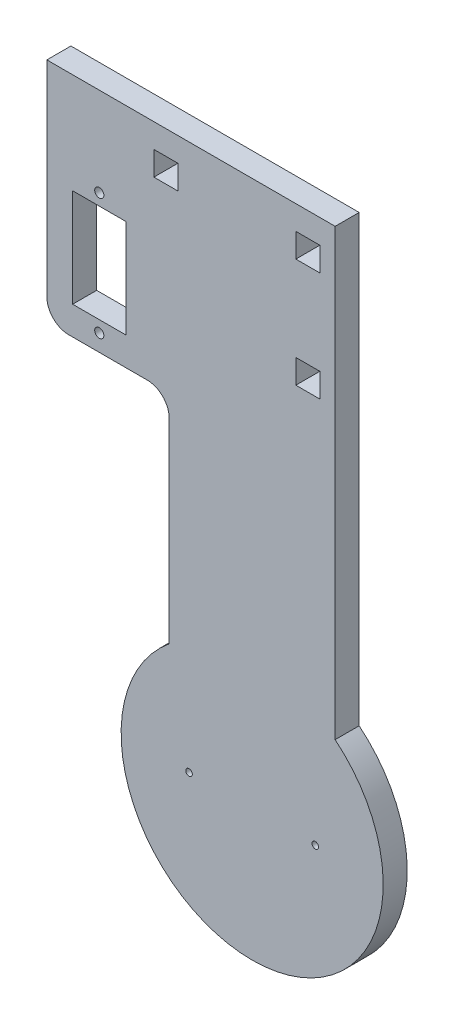
SolidWorks part; units mm, degrees
material "ﾁｰｸ材"
ref_plane "正面" through (0, 0, 0) normal (0, 0, 1) x (1, 0, 0)
ref_plane "平面" through (0, 0, 0) normal (0, 1, 0) x (1, 0, 0)
ref_plane "右側面" through (0, 0, 0) normal (1, 0, 0) x (0, 0, -1)
sketch "ｽｹｯﾁ1" plane through (0, 0, 0) normal (0, 0, 1) x (1, 0, 0)
  line L0 (19, 125) -> (-47, 125)
  line L1 (-19, 73) -> (-19, 23.2164)
  line L2 (19, 125) -> (19, 23.2164)
  line L4 (-47, 125) -> (-47, 73)
  line L6 (-47, 73) -> (-19, 73)
  arc A0 (-19, 23.2164) -> (19, 23.2164) centre (0, 0) ccw
  point P8 (-19, 75.5757)
  dimension "D1" = 60
  dimension "D2" = 125
  dimension "D3" = 19
  dimension "D4" = 47
  dimension "D5" = 52
extrude "ﾎﾞｽ - 押し出し1" add sketch "ｽｹｯﾁ1" along normal blind 5.5
sketch "ｽｹｯﾁ2" plane through (0, 0, 5.5) normal (0, 0, 1) x (1, 0, 0)
  line L0 (19, 125) -> (-47, 125) construction
  line L1 (-28.9, 79.5) -> (-41.1, 79.5)
  line L2 (-28.9, 79.5) -> (-28.9, 102)
  line L3 (-28.9, 102) -> (-41.1, 102)
  line L4 (-41.1, 79.5) -> (-41.1, 102)
  line L5 (-28.9, 79.5) -> (-41.1, 102) construction
  line L6 (-28.9, 102) -> (-41.1, 79.5) construction
  point P0 (-35, 90.75)
  dimension "D1" = 12.2
  dimension "D2" = 22.5
  dimension "D3" = 35
  dimension "D4" = 23
extrude "ｶｯﾄ - 押し出し1" cut sketch "ｽｹｯﾁ2" against normal through all
sketch "ｽｹｯﾁ3" plane through (0, 0, 5.5) normal (0, 0, 1) x (1, 0, 0)
  line L0 (0, 0) -> (0, 22.4882) construction
sketch "ｽｹｯﾁ4" plane through (0, 0, 5.5) normal (0, 0, 1) x (1, 0, 0)
  line L0 (19, 125) -> (-47, 125) construction
  line L1 (15.5, 114) -> (10, 114)
  line L2 (15.5, 114) -> (15.5, 119.5)
  line L3 (15.5, 119.5) -> (10, 119.5)
  line L4 (10, 114) -> (10, 119.5)
  line L5 (15.5, 114) -> (10, 119.5) construction
  line L6 (15.5, 119.5) -> (10, 114) construction
  line L7 (0, 0) -> (0, 22.4882) construction
  line L8 (-17, 114) -> (-22.5, 114)
  line L9 (-17, 114) -> (-17, 119.5)
  line L10 (-17, 119.5) -> (-22.5, 119.5)
  line L11 (-22.5, 114) -> (-22.5, 119.5)
  line L12 (-17, 114) -> (-22.5, 119.5) construction
  line L13 (-17, 119.5) -> (-22.5, 114) construction
  line L14 (-28.9, 102) -> (-41.1, 102) construction
  line L15 (15.5, 89) -> (10, 89)
  line L16 (15.5, 89) -> (15.5, 94.5)
  line L17 (15.5, 94.5) -> (10, 94.5)
  line L18 (10, 89) -> (10, 94.5)
  line L19 (15.5, 89) -> (10, 94.5) construction
  line L20 (15.5, 94.5) -> (10, 89) construction
  line L21 (-41.1, 79.5) -> (-28.9, 79.5) construction
  circle A0 centre (-35, 104.65) radius 1.05
  circle A1 centre (-35, 76.85) radius 1.05
  point P0 (12.75, 116.75)
  point P9 (-19.75, 116.75)
  point P14 (12.75, 91.75)
  point P28 (-35, 79.5)
  dimension "D11" = 2.1
  dimension "D1" = 5.5
  dimension "D2" = 5.5
  dimension "D3" = 5.5
  dimension "D4" = 10
  dimension "D5" = 5.5
  dimension "D6" = 5.5
  dimension "D7" = 27
  dimension "D8" = 5.5
  dimension "D9" = 5.5
  dimension "D10" = 25
  dimension "D12" = 2.65
  dimension "D13" = 2.65
extrude "ｶｯﾄ - 押し出し2" cut sketch "ｽｹｯﾁ4" against normal through all
fillet "ﾌｨﾚｯﾄ1" radius 5 1 edges at (-47, 73, 2.75)
fillet "ﾌｨﾚｯﾄ2" radius 5 1 edges at (-19, 73, 2.75)
sketch "ｽｹｯﾁ5" plane through (0, 0, 5.5) normal (0, 0, 1) x (1, 0, 0)
  circle A0 centre (14.45, 0) radius 0.75
  circle A1 centre (-14.45, 0) radius 0.75
  point P4 (13.9723, -3.8763)
  dimension "D1" = 14.45
  dimension "D2" = 1.5
  dimension "D3" = 14.45
extrude "ｶｯﾄ - 押し出し3" cut sketch "ｽｹｯﾁ5" against normal through all
